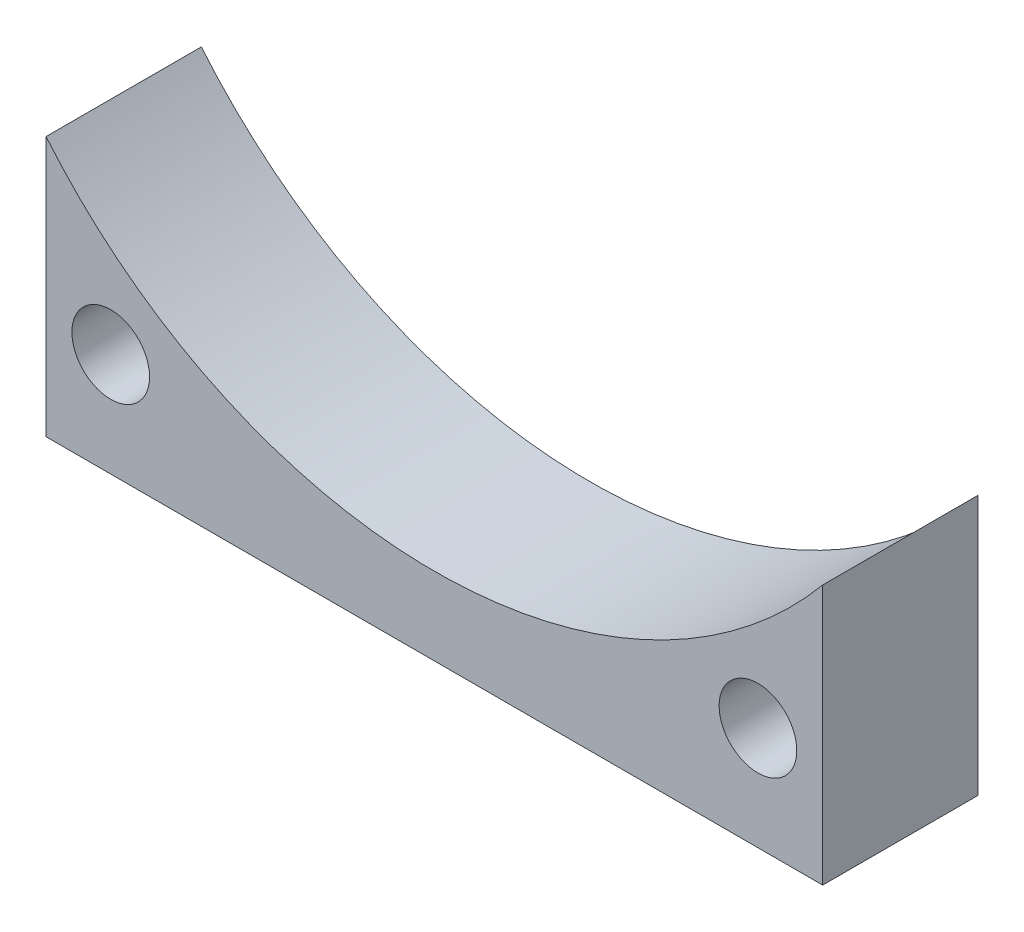
SolidWorks part; units mm, degrees
ref_plane "Plan de face" through (0, 0, 0) normal (0, 0, 1) x (1, 0, 0)
ref_plane "Plan de dessus" through (0, 0, 0) normal (0, 1, 0) x (1, 0, 0)
ref_plane "Plan de droite" through (0, 0, 0) normal (1, 0, 0) x (0, 0, -1)
sketch "Esquisse1" plane through (0, 0, 0) normal (0, 0, 1) x (1, 0, 0)
  line L1 (0, 0) -> (60, 0)
  line L2 (0, 0) -> (0, 25)
  line L3 (0, 25) -> (60, 25)
  line L4 (60, 0) -> (60, 25)
  dimension "D1" = 25
  dimension "D2" = 60
extrude "Boss.-Extru.1" add sketch "Esquisse1" along normal blind 12
sketch "Esquisse2" plane through (0, 0, 12) normal (0, 0, 1) x (1, 0, 0)
  line L0 (30, 0) -> (30, 25) construction
  line L1 (0, 0) -> (60, 0) construction
  line L2 (60, 25) -> (0, 25) construction
  line L3 (5, 8) -> (30, 8) construction
  circle A0 centre (5, 8) radius 3
  circle A1 centre (55, 8) radius 3
  point P11 (0, 0)
  point P12 (30, 17.0455)
  dimension "D1" = 6
  dimension "D2" = 25
  dimension "D3" = 8
extrude "Enlèv. mat.-Extru.1" cut sketch "Esquisse2" against normal through all both and the other way through all
sketch "Esquisse3" plane through (0, 0, 12) normal (0, 0, 1) x (1, 0, 0)
  line L0 (30, 0) -> (30, 45) construction
  line L1 (0, 0) -> (60, 0) construction
  line L2 (60, 25) -> (0, 25) construction
  circle A0 centre (30, 45) radius 39
  dimension "D1" = 78
  dimension "D2" = 20
extrude "Enlèv. mat.-Extru.2" cut sketch "Esquisse3" against normal up to next
